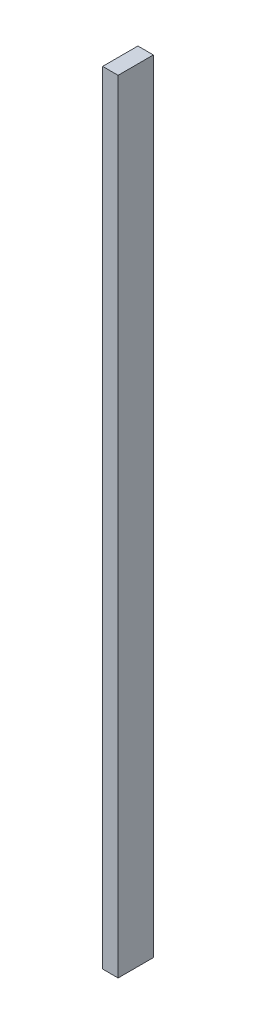
SolidWorks part; units mm, degrees
material "6061-T6 (SS)"
ref_plane "Front" through (0, 0, 0) normal (0, 0, 1) x (1, 0, 0)
ref_plane "Top" through (0, 0, 0) normal (0, 1, 0) x (1, 0, 0)
ref_plane "Right" through (0, 0, 0) normal (1, 0, 0) x (0, 0, -1)
sketch "Sketch1" plane through (0, 0, 0) normal (0, 1, 0) x (1, 0, 0)
  line L1 (-50.8, 115.8875) -> (50.8, 115.8875)
  line L2 (-50.8, 115.8875) -> (-50.8, -115.8875)
  line L3 (-50.8, -115.8875) -> (50.8, -115.8875)
  line L4 (50.8, 115.8875) -> (50.8, -115.8875)
  line L5 (-50.8, 115.8875) -> (50.8, -115.8875) construction
  line L6 (-50.8, -115.8875) -> (50.8, 115.8875) construction
  point P0 (0, 0)
  dimension "D1" = 101.6
  dimension "D2" = 231.775
extrude "Boss-Extrude1" add sketch "Sketch1" along normal blind 5137.15
